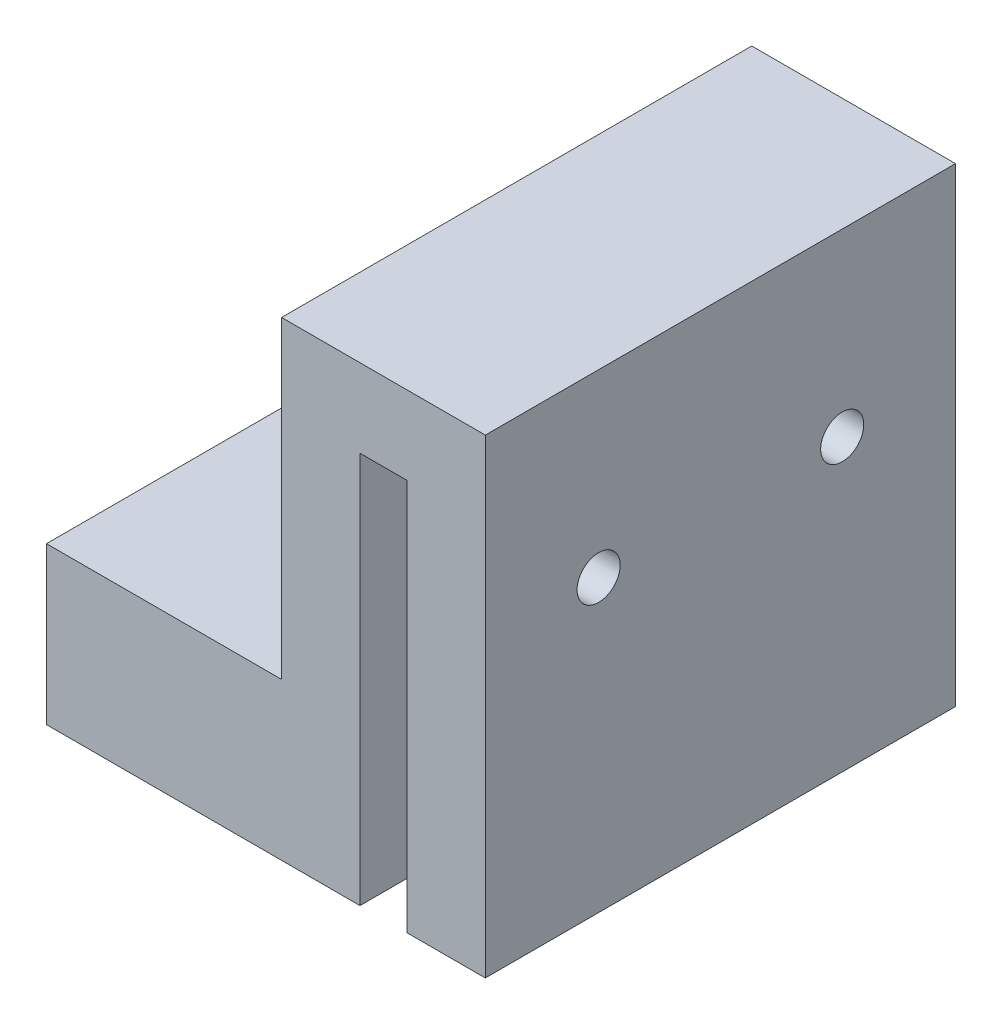
SolidWorks part; units mm, degrees
ref_plane "Front Plane" through (0, 0, 0) normal (0, 0, 1) x (1, 0, 0)
ref_plane "Top Plane" through (0, 0, 0) normal (0, 1, 0) x (1, 0, 0)
ref_plane "Right Plane" through (0, 0, 0) normal (1, 0, 0) x (0, 0, -1)
sketch "Sketch1" plane through (0, 0, 0) normal (0, 0, 1) x (1, 0, 0)
  line L0 (0, 0) -> (0, 60)
  line L1 (0, 60) -> (-26, 60)
  line L2 (-26, 60) -> (-26, 20)
  line L3 (-26, 20) -> (-56, 20)
  line L4 (-56, 20) -> (-56, 0)
  line L5 (-56, 0) -> (-16, 0)
  line L6 (-10, 0) -> (0, 0)
  line L8 (-10, 0) -> (-10, 50)
  line L9 (-10, 50) -> (-16, 50)
  line L10 (-16, 0) -> (-16, 50)
  dimension "D1" = 60
  dimension "D2" = 10
  dimension "30" = 40
  dimension "D3" = 6
  dimension "D4" = 10
  dimension "D5" = 30
  dimension "D6" = 10
extrude "Boss-Extrude1" add sketch "Sketch1" along normal blind 60
sketch "Sketch4" plane through (-26, 0, 0) normal (-1, 0, 0) x (0, 0, 1)
  line L0 (14.4586, 37.0312) -> (45.5414, 37.0312) construction
  line L1 (60, 60) -> (0, 60) construction
  circle A0 centre (14.4586, 37.0312) radius 2.75
  circle A1 centre (45.5414, 37.0312) radius 2.75
  point P6 (30, 60)
  point P7 (30, 37.0312)
  dimension "D1" = 5.5
extrude "Cut-Extrude3" cut sketch "Sketch4" against normal blind 30
sketch "Sketch5" plane through (0, 60, 0) normal (0, 1, 0) x (1, 0, 0)
  line L0 (-37.2, 0) -> (-37.2, -60) construction
  line L4 (-26, 0) -> (-56, 0)
  line L5 (-56, 0) -> (-56, -60)
  line L6 (-56, -60) -> (-26, -60)
  line L7 (-26, -60) -> (-26, 0)
  line L8 (-26, 0) -> (-56, 0)
  line L9 (-56, 0) -> (-56, -60)
  line L10 (-56, -60) -> (-26, -60)
  line L11 (-26, -60) -> (-26, 0)
  circle A0 centre (-37.2, -38) radius 2
  circle A1 centre (-37.2, -22) radius 2
  circle A2 centre (-37.2, -22) radius 4
  circle A3 centre (-37.2, -38) radius 4
  point P13 (-41, -21.5337)
  point P14 (-37.2, -30)
  dimension "D2" = 8
  dimension "D3" = 4
  dimension "D4" = 16
  dimension "D5" = 8
  dimension "D6" = 11.2
  dimension "D1" = 0
extrude "Boss-Extrude2" add sketch "Sketch5" against normal blind 10 from surface contours A1 L0 | L0 A1 | A0 L0 | L0 A0 region at (-36.3512, 60, 22) region at (-38.0488, 60, 22) region at (-36.3512, 60, 38) region at (-38.0488, 60, 38) starting at face at (-36, 0, 30)
